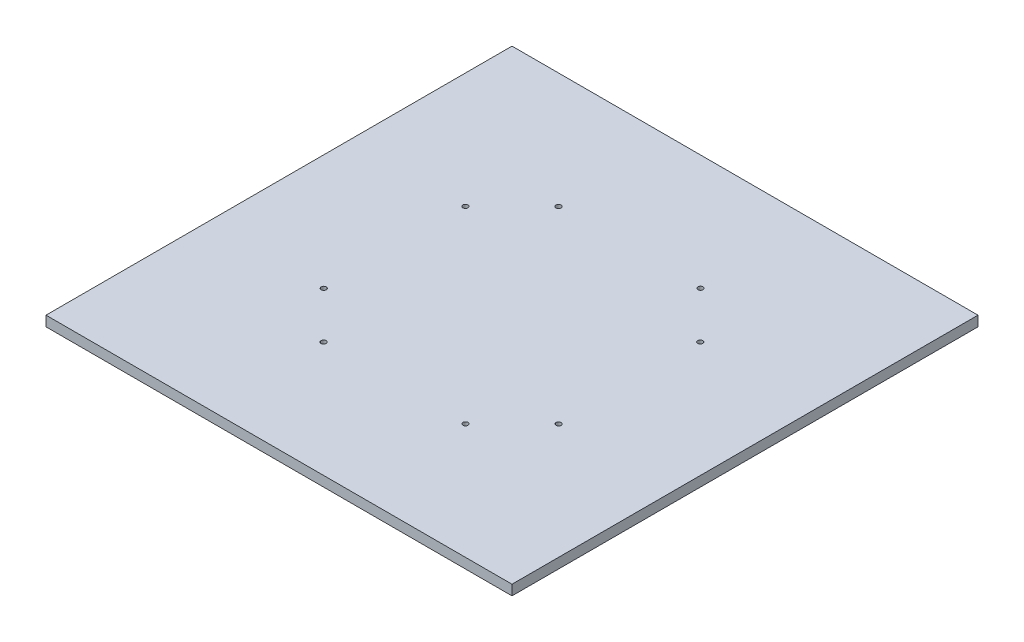
SolidWorks part; units mm, degrees
ref_plane "Front Plane" through (0, 0, 0) normal (0, 0, 1) x (1, 0, 0)
ref_plane "Top Plane" through (0, 0, 0) normal (0, 1, 0) x (1, 0, 0)
ref_plane "Right Plane" through (0, 0, 0) normal (1, 0, 0) x (0, 0, -1)
sketch "Sketch1" plane through (0, 0, 0) normal (0, 1, 0) x (1, 0, 0)
  line L1 (-146.05, 146.05) -> (146.05, 146.05)
  line L2 (-146.05, 146.05) -> (-146.05, -146.05)
  line L3 (-146.05, -146.05) -> (146.05, -146.05)
  line L4 (146.05, 146.05) -> (146.05, -146.05)
  line L5 (-146.05, 146.05) -> (146.05, -146.05) construction
  line L6 (-146.05, -146.05) -> (146.05, 146.05) construction
  point P0 (0, 0)
  dimension "D1" = 292.1
extrude "Boss-Extrude1" add sketch "Sketch1" along normal blind 6.35
sketch "Sketch2" plane through (0, 6.35, 0) normal (0, 1, 0) x (1, 0, 0)
  line L0 (146.05, -146.05) -> (146.05, 146.05) construction
  line L1 (-146.05, -146.05) -> (146.05, -146.05) construction
  circle A0 centre (73.66, -44.45) radius 1.6
  circle A1 centre (44.43, -73.57) radius 1.6
  point P8 (69.684, -65.3055)
  point P11 (55.8946, -146.05)
  dimension "D5" = 3.2
  dimension "D1" = 72.39
  dimension "D2" = 101.6
  dimension "D3" = 101.62
  dimension "D4" = 72.48
extrude "Cut-Extrude1" cut sketch "Sketch2" against normal through all
sketch "Sketch4" plane through (0, 6.35, 0) normal (0, 1, 0) x (1, 0, 0)
  line L0 (-146.05, -146.05) -> (146.05, 146.05) construction
  line L1 (146.05, 146.05) -> (-146.05, 146.05) construction
  line L2 (146.05, -146.05) -> (146.05, 146.05) construction
  line L3 (146.05, -146.05) -> (0, 0) construction
ref_axis "Axis1" through (0, 6.35, 0) along (0, 1, 0)
pattern_circular "CirPattern1" count 4 over 360 about axis through (0, 6.35, 0) along (0, 1, 0) of "Cut-Extrude1"
